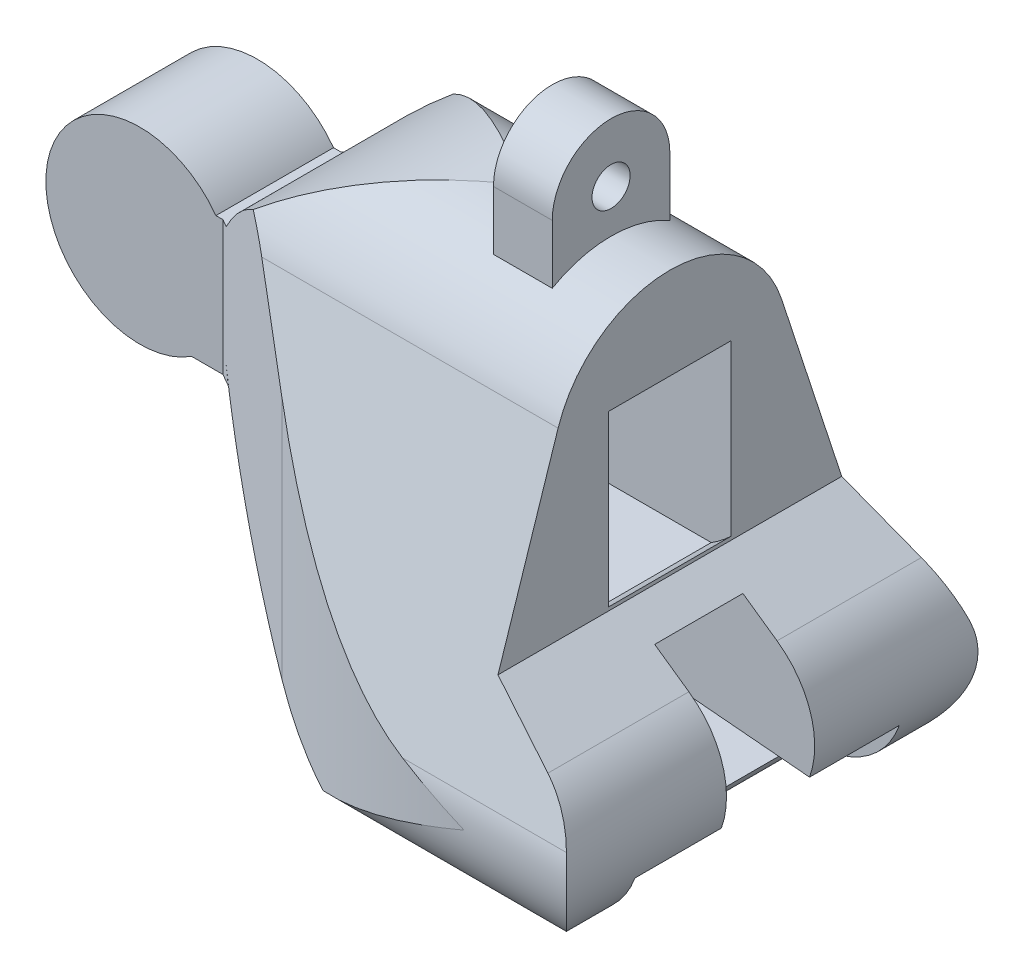
SolidWorks part; units mm, degrees
material "Polycarbonate"
ref_plane "Front Plane" through (0, 0, 0) normal (0, 0, 1) x (1, 0, 0)
ref_plane "Top Plane" through (0, 0, 0) normal (0, 1, 0) x (1, 0, 0)
ref_plane "Right Plane" through (0, 0, 0) normal (1, 0, 0) x (0, 0, -1)
sketch "Sketch2" plane through (0, 0, 0) normal (0, 0, 1) x (1, 0, 0)
  line L0 (4.4873, -2.3813) -> (4.4873, 2.3813)
  arc A0 (4.4873, 2.3813) -> (4.4873, -2.3813) centre (0, 0) ccw
  dimension "D1" = 10.16
  dimension "D2" = 4.7625
extrude "Boss-Extrude1" add sketch "Sketch2" along normal blind 6.35
sketch "Sketch3" plane through (0, 0, 0) normal (0, 0, 1) x (1, 0, 0)
  line L0 (4.4873, -2.3813) -> (4.4873, 2.3813) construction
  line L1 (4.4873, 9.525) -> (25.4423, 9.525)
  line L2 (4.4873, 9.525) -> (4.4873, -15.875)
  line L3 (4.4873, -15.875) -> (25.4423, -15.875)
  line L4 (25.4423, 9.525) -> (25.4423, -4.7625)
  line L5 (4.4873, 9.525) -> (25.4423, -15.875) construction
  line L6 (4.4873, -15.875) -> (25.4423, 9.525) construction
  line L7 (25.4423, -4.7625) -> (41.3126, -15.875)
  line L8 (41.3126, -15.875) -> (25.4423, -15.875)
  point P0 (14.9648, -3.175)
  dimension "D1" = 20.955
  dimension "D2" = 25.4
  dimension "D3" = 9.525
  dimension "D4" = 55
  dimension "D5" = 11.1125
extrude "Boss-Extrude2" add sketch "Sketch3" along normal offset from surface (22.225 mm away) 7.9375 from offset 7.9375 separate body up to face at (-0.2963, 0, 6.35) offset beyond the face yes offset against normal yes
sketch "Sketch4" plane through (0, 9.525, 0) normal (0, 1, 0) x (1, 0, 0)
  line L0 (4.4873, -6.35) -> (11.9942, -10.6841)
  line L1 (4.4873, 0) -> (11.9942, 4.3341)
  line L2 (4.4873, -14.2875) -> (4.4873, 7.9375) construction
  line L4 (25.4423, -14.2875) -> (4.4873, -14.2875) construction
  line L5 (25.4423, 7.9375) -> (4.4873, 7.9375) construction
  line L6 (4.4873, -14.2875) -> (4.4873, -6.35)
  line L7 (25.4423, 7.9375) -> (4.4873, 7.9375)
  line L8 (25.4423, -14.2875) -> (4.4873, -14.2875)
  line L9 (4.4873, 0) -> (4.4873, 7.9375)
  arc A0 (11.9942, -10.6841) -> (25.4423, -14.2875) centre (25.4423, 12.6088) ccw
  arc A1 (11.9942, 4.3341) -> (25.4423, 7.9375) centre (25.4423, -18.9588) cw
  dimension "D1" = 60
  dimension "D2" = 60
extrude "Cut-Extrude1" cut sketch "Sketch4" against normal through all
sketch "Sketch5" plane through (0, 0, 0) normal (0, 0, 1) x (1, 0, 0)
  line L0 (41.3126, -15.875) -> (25.4423, -4.7625) construction
  line L2 (11.9942, -15.875) -> (25.4423, -15.875) construction
  line L3 (22.7376, -15.875) -> (26.2079, -15.875) construction
  line L4 (25.4423, -15.875) -> (41.3126, -15.875) construction
  line L5 (41.3126, -15.875) -> (25.4423, -4.7625) construction
  line L6 (4.4873, -15.875) -> (4.4873, -2.3813)
  line L7 (25.4423, 9.525) -> (17.5048, 9.525) construction
  line L8 (25.4423, 9.525) -> (11.9942, 9.525) construction
  line L10 (4.4873, 2.3813) -> (4.4873, -2.3813) construction
  line L11 (4.4873, 2.3813) -> (4.4873, 9.525)
  line L12 (4.4873, 9.525) -> (17.5048, 9.525)
  line L13 (26.2079, -15.875) -> (41.3126, -15.875)
  line L16 (41.3126, -15.875) -> (28.9396, -7.2113)
  line L17 (4.4873, -2.3813) -> (4.8365, -3.3405)
  line L18 (4.4873, -15.875) -> (22.7376, -15.875)
  arc A1 (17.5048, 9.525) -> (4.4873, 2.3813) centre (17.5048, -5.9073) ccw
  arc A3 (4.8365, -3.3405) -> (22.7376, -15.875) centre (22.7376, 3.175) ccw
  arc A4 (26.2079, -15.875) -> (28.9396, -7.2113) centre (26.2079, -11.1125) ccw
  dimension "D1" = 20
  dimension "D2" = 7.9375
  dimension "D3" = 4.7625
  dimension "D4" = 19.05
extrude "Cut-Extrude2" cut sketch "Sketch5" along normal blind 25.24 from surface contours L18 A4 A3 L17 L6 | A4 A3 L13 L16 | A1 L12 L11 region at (8.6708, -12.2776, 0) region at (7.5722, 7.5055, 0) region at (33.8275, -13.515, 0) starting at face at (30.7324, -12.1708, -7.9375)
sketch "Sketch7" plane through (25.4423, 0, 0) normal (1, 0, 0) x (0, 0, -1)
  line L0 (-3.175, 9.525) -> (-3.175, -7.9375) construction
  line L2 (-9.525, -15.875) -> (3.175, -15.875) construction
  line L3 (3.175, -15.875) -> (7.9375, -15.875)
  line L4 (6.7396, 9.525) -> (-13.0896, 9.525) construction
  line L5 (7.9375, -4.7625) -> (7.9375, 9.525) construction
  line L10 (7.9375, 9.525) -> (-14.2875, 9.525)
  line L11 (7.9375, -4.7625) -> (7.9375, 9.525)
  line L12 (-9.525, -15.875) -> (-14.2875, -15.875)
  line L14 (-14.0509, -9.6301) -> (-9.2096, 5.1515)
  line L15 (7.7009, -9.6301) -> (2.8596, 5.1515)
  line L18 (7.9375, -4.7625) -> (7.9375, -15.875)
  line L19 (7.9375, -15.875) -> (7.9375, -4.7625)
  line L20 (-14.2875, -15.875) -> (-14.2875, 9.525)
  arc A0 (-9.2096, 5.1515) -> (2.8596, 5.1515) centre (-3.175, 3.175) cw
  arc A3 (-14.0509, -9.6301) -> (-9.525, -15.875) centre (-9.525, -11.1125) ccw
  arc A4 (7.7009, -9.6301) -> (3.175, -15.875) centre (3.175, -11.1125) cw
  point P12 (-3.175, 9.525)
  line M3 (-14.2875, 9.525) -> (-14.2875, -4.7625)
  line M5 (7.9375, -4.7625) -> (7.9375, 9.525)
  line M6 (7.9375, 9.525) -> (-14.2875, 9.525)
  line M30 (-14.2875, -4.7625) -> (7.9375, -4.7625)
  dimension "D1" = 6.35
  dimension "D2" = 4.7625
  dimension "D3" = 25.4
  dimension "D4" = 4.7625
extrude "Cut-Extrude7" cut sketch "Sketch7" against normal blind 19.05 and the other way blind 10 contours A3 L20 L12 | L19 A4 L3 region at (25.4423, -14.8112, -6.8737) region at (25.4423, -14.8112, 13.2237)
extrude "Cut-Extrude10" cut sketch "Sketch7<4>" against normal blind 17.78 and the other way blind 10.16 contours L14 A0 L10 M3 M30 | A0 L15 M6 M30 M5 | L15 A4 L18 M30 | A3 L14 L20 M30 region at (25.4423, -6.6478, -7.3305) region at (25.4423, 4.0189, -5.3307) region at (25.4423, 4.0189, 11.6807) region at (25.4423, -6.6478, 13.6805)
sketch "Sketch7<4>" plane through (25.4423, 0, 0) normal (1, 0, 0) x (0, 0, -1) same geometry as "Sketch7"
sketch "Sketch8" plane through (0, 0, 6.35) normal (0, 0, 1) x (1, 0, 0)
  line L0 (25.4423, 4.572) -> (25.4423, -4.572)
  line L2 (17.6953, 5.4005) -> (24.3758, 5.4005)
  line L3 (24.3758, -5.4005) -> (17.6953, -5.4005)
  line L4 (17.6953, 5.4005) -> (17.6953, -5.4005)
  line L5 (25.4423, -4.7625) -> (25.4423, 5.1515) construction
  arc A0 (25.4423, 4.572) -> (24.3758, 5.4005) centre (21.0356, 0) ccw
  arc A1 (25.4423, 4.572) -> (25.4423, -4.572) centre (21.0356, 0) ccw
  arc A2 (24.3758, -5.4005) -> (25.4423, -4.572) centre (21.0356, 0) ccw
  arc A3 (25.4423, 4.572) -> (25.4423, -4.572) centre (21.0356, 0) ccw
  circle A4 centre (21.0356, 0) radius 5.08 construction
  point P12 (17.6953, 0)
  dimension "D1" = 12.7
  dimension "D6" = 10.16
  dimension "D2" = 9.144
  dimension "D3" = 3.3403
extrude "Cut-Extrude8" cut sketch "Sketch8" against normal blind 6.604 from offset 0.127 contours L3 A1 L0 A0 L2 L4 region at (21.5339, 0, 6.35)
sketch "Sketch12" plane through (25.4423, 0, 0) normal (1, 0, 0) x (0, 0, -1)
  line L1 (-6.35, 8.6743) -> (0, 8.6743)
  line L2 (-6.35, 8.6743) -> (-6.35, 11.8493)
  line L4 (0, 8.6743) -> (0, 11.8493)
  arc A0 (2.8596, 5.1515) -> (-9.2096, 5.1515) centre (-3.175, 3.175) ccw construction
  arc A1 (2.8596, 5.1515) -> (-9.2096, 5.1515) centre (-3.175, 3.175) ccw construction
  arc A2 (0, 11.8493) -> (-6.35, 11.8493) centre (-3.175, 11.8493) ccw
  point P8 (-3.175, 8.6743)
  point P9 (-3.175, 9.525)
  dimension "D1" = 6.35
  dimension "D2" = 3.175
extrude "Boss-Extrude3" add sketch "Sketch12" against normal blind 3.175 from offset 3.175 offset against normal yes
hole_wizard "#1 Clearance Hole1" positions "Sketch13" profile "Sketch14" hole size "#1" standard "ANSI Inch" end condition up to next
sketch "Sketch13" plane through (22.2673, 0, 0) normal (1, 0, 0) x (0, 0, -1)
  point P0 (-3.175, 11.8493)
sketch "Sketch14" plane through (22.2673, 11.8493, 3.175) normal (0, 1, 0) x (0, 0, -1)
  line L0 (0, 0) -> (0, 3.176)
  line L1 (0, 3.176) -> (1.0287, 3.176)
  line L2 (1.0287, 3.176) -> (1.0287, 0)
  line L5 (1.0287, 0) -> (0, 0)
  line L11 (0, -6.35) -> (0, 107.95) construction
  dimension "Thru Hole Dia." = 2.0574
  dimension "Thru Hole Depth" = 3.176
ref_plane "Plane1" through (30.9704, 0, 0) normal (1, 0, 0) x (0, 0, -1)
sketch "Sketch15" plane through (30.9704, 0, 0) normal (1, 0, 0) x (0, 0, -1)
  line L1 (-5.6442, -7.2113) -> (-0.8817, -7.2113)
  line L2 (-5.6442, -7.2113) -> (-5.6442, -11.9738)
  line L3 (-5.6442, -11.9738) -> (-0.8817, -11.9738)
  line L4 (-0.8817, -7.2113) -> (-0.8817, -11.9738)
  line L5 (-5.6442, -7.2113) -> (-0.8817, -11.9738) construction
  line L6 (-5.6442, -11.9738) -> (-0.8817, -7.2113) construction
  line L7 (-13.2587, -7.2113) -> (6.9087, -7.2113) construction
  point P0 (-3.2629, -9.5925)
  dimension "D1" = 4.7625
  dimension "D2" = 4.7625
extrude "Cut-Extrude15" cut sketch "Sketch15" against normal up to surface (8.7031 mm away) up to face at (22.2673, 11.8493, 2.1463)
sketch "Sketch16" plane through (22.2673, 0, 0) normal (1, 0, 0) x (0, 0, -1)
  line L4 (-0.8817, -11.9738) -> (-0.8817, -7.2113)
  line L5 (-0.8817, -7.2113) -> (-5.6442, -7.2113)
  line L6 (-5.6442, -7.2113) -> (-5.6442, -11.9738)
  line L7 (-5.6442, -11.9738) -> (-0.8817, -11.9738)
  line L8 (-0.8817, -11.9738) -> (-0.8817, -7.2113)
  line L9 (-0.8817, -7.2113) -> (-5.6442, -7.2113)
  line L10 (-5.6442, -7.2113) -> (-5.6442, -11.9738)
  line L11 (-5.6442, -11.9738) -> (-0.8817, -11.9738)
  dimension "D1" = 0
extrude "Cut-Extrude16" cut sketch "Sketch16" against normal through all from surface starting at face at (19.0923, 11.8493, 2.1463)
hole_wizard "#1 Clearance Hole2" positions "Sketch17" profile "Sketch18" hole size "#1" standard "ANSI Inch" end condition up to next
sketch "Sketch17" plane through (22.2673, 0, 0) normal (1, 0, 0) x (0, 0, -1)
  line L8 (-0.8817, -11.9738) -> (-0.8817, -7.2113)
  line L9 (-0.8817, -7.2113) -> (-5.6442, -7.2113)
  line L10 (-5.6442, -7.2113) -> (-5.6442, -11.9738)
  line L11 (-5.6442, -11.9738) -> (-0.8817, -11.9738)
  line L12 (-0.8817, -11.9738) -> (-0.8817, -7.2113)
  line L13 (-0.8817, -7.2113) -> (-5.6442, -7.2113)
  line L14 (-5.6442, -7.2113) -> (-5.6442, -11.9738)
  line L15 (-5.6442, -11.9738) -> (-0.8817, -11.9738)
  line L16 (-5.6442, -7.2113) -> (-0.8817, -11.9738) construction
  point P0 (-3.2629, -9.5925)
  dimension "D1" = 0
sketch "Sketch18" plane through (22.2673, -9.5925, 3.2629) normal (0, 1, 0) x (0, 0, -1)
  line L0 (0, 0) -> (0, 3.176)
  line L1 (0, 3.176) -> (1.0287, 3.176)
  line L2 (1.0287, 3.176) -> (1.0287, 0)
  line L5 (1.0287, 0) -> (0, 0)
  line L11 (0, -6.35) -> (0, 107.95) construction
  dimension "Thru Hole Dia." = 2.0574
  dimension "Thru Hole Depth" = 3.176
sketch "Sketch19" plane through (0, 0, 0.8817) normal (0, 0, 1) x (1, 0, 0)
  line L0 (19.0923, -11.9738) -> (13.484, -13.4765)
  line L1 (19.0923, -7.2113) -> (6.083, -6.0731)
  line L2 (22.2673, -7.2113) -> (27.0929, -5.9183)
  line L3 (11.187, -11.9738) -> (19.0923, -11.9738)
  line L4 (19.0923, -11.9738) -> (19.0923, -7.2113)
  line L5 (19.0923, -7.2113) -> (6.768, -7.2113)
  line L6 (11.187, -11.9738) -> (19.0923, -11.9738) construction
  line L7 (19.0923, -11.9738) -> (19.0923, -7.2113)
  line L8 (19.0923, -7.2113) -> (6.768, -7.2113) construction
  line L9 (28.9396, -7.2113) -> (25.4423, -4.7625) construction
  line L10 (28.9396, -7.2113) -> (27.0929, -5.9183)
  line L11 (22.2673, -11.9738) -> (30.6941, -12.711)
  line L13 (28.9396, -7.2113) -> (22.2673, -7.2113)
  line L14 (22.2673, -7.2113) -> (22.2673, -11.9738)
  line L15 (22.2673, -11.9738) -> (30.8919, -11.9738)
  line L17 (28.9396, -7.2113) -> (22.2673, -7.2113) construction
  line L18 (22.2673, -7.2113) -> (22.2673, -11.9738)
  line L19 (22.2673, -11.9738) -> (30.8919, -11.9738) construction
  arc A1 (6.768, -7.2113) -> (11.187, -11.9738) centre (22.7376, 3.175) ccw
  arc A6 (4.8365, -3.3405) -> (11.9942, -12.5565) centre (22.7376, 3.175) ccw construction
  arc A7 (6.083, -6.0731) -> (13.484, -13.4765) centre (22.7376, 3.175) ccw
  arc A8 (26.2079, -15.875) -> (30.7338, -9.6301) centre (26.2079, -11.1125) ccw construction
  arc A9 (30.8919, -11.9738) -> (28.9396, -7.2113) centre (26.2079, -11.1125) ccw
  arc A12 (30.6941, -12.711) -> (28.9396, -7.2113) centre (26.2079, -11.1125) ccw
  dimension "D2" = 15
  dimension "D3" = 5
  dimension "D5" = 15
  dimension "D6" = 5
  dimension "D1" = 0
  dimension "D4" = 0
extrude "Cut-Extrude17" cut sketch "Sketch19" along normal up to surface (4.7625 mm away) up to face at (13.9838, -9.64, 5.6442)
sketch "Sketch21" plane through (0, 0, 0) normal (0, 0, -1) x (-1, 0, 0)
  line L0 (-4.8365, -3.3405) -> (-4.4873, -2.3813) construction
  line L1 (-5.1668, -4.2482) -> (-4.4873, -2.3813)
  line L2 (-5.1668, -4.2482) -> (-2.7856, -4.2482)
  line L3 (-4.1043, 2.9935) -> (-4.898, 2.9935)
  line L4 (-4.4873, 2.3813) -> (-4.4873, 2.9935)
  line L5 (-4.4873, -2.3813) -> (-4.4873, -4.2482)
  arc A0 (-4.4873, 2.3813) -> (-8.3449, 6.5125) centre (-17.5048, -5.9073) ccw construction
  arc A1 (-4.4873, -2.3813) -> (-4.4873, 2.3813) centre (0, 0) ccw construction
  arc A2 (-4.4873, 2.3813) -> (-4.898, 2.9935) centre (-17.5048, -5.9073) ccw
  arc A3 (-4.4873, -2.3813) -> (-2.7856, -4.2482) centre (0, 0) ccw
  arc A4 (-4.1043, 2.9935) -> (-4.4873, 2.3813) centre (0, 0) ccw
  dimension "D1" = 2.3812
  dimension "D2" = 0.7937
extrude "Boss-Extrude5" add sketch "Sketch21" along normal up to surface contours A2 L4 L3 | L5 L1 L2 region at (4.7138, -3.6259, 0) region at (4.6231, 2.7912, 0) up to face at (7.8201, -0.564, -1.9242)
extrude "Boss-Extrude6" add sketch "Sketch21<3>" against normal up to surface (6.35 mm away) contours A4 L3 A2 | L1 L2 A3 up to face at (-0.2963, 0, 6.35)
sketch "Sketch21<3>" plane through (0, 0, 0) normal (0, 0, -1) x (-1, 0, 0) same geometry as "Sketch21"
sketch "Sketch22" plane through (0, 0, 6.35) normal (0, 0, 1) x (1, 0, 0)
  line L0 (4.4873, 2.3812) -> (4.5012, 2.9935)
  line L1 (4.1043, 2.9935) -> (4.898, 2.9935) construction
  line L2 (4.5012, 2.9935) -> (4.898, 2.9935)
  line L3 (4.898, 2.9935) -> (4.4873, 2.3812)
  line L4 (4.4873, -2.3812) -> (4.4873, -4.2482)
  line L5 (5.1668, -4.2482) -> (2.7856, -4.2482) construction
  line L6 (4.4873, -4.2482) -> (5.1668, -4.2482)
  line L7 (5.1668, -4.2482) -> (4.4873, -2.3812)
extrude "Boss-Extrude8" add sketch "Sketch22" along normal up to surface (0.2371 mm away) up to face at (7.8201, -0.564, 8.2742)
sketch "Sketch28" plane through (0, 0, 0) normal (0, 0, 1) x (1, 0, 0)
  line L0 (22.2673, -11.9738) -> (30.6941, -12.711) construction
  line L1 (26.2079, -15.875) -> (22.7376, -15.875) construction
  line L2 (29.0309, -12.5655) -> (30.6941, -12.711)
  line L3 (26.2079, -15.875) -> (22.7376, -15.875)
  line L4 (13.484, -13.4765) -> (19.0923, -11.9738) construction
  line L5 (13.484, -13.4765) -> (15.8082, -12.8538)
  line L6 (26.2079, -14.2875) -> (22.7376, -14.2875)
  arc A0 (26.2079, -15.875) -> (30.7338, -9.6301) centre (26.2079, -11.1125) ccw construction
  arc A1 (11.9942, -12.5565) -> (16.1833, -14.712) centre (22.7376, 3.175) ccw construction
  arc A2 (16.1833, -14.712) -> (22.7376, -15.875) centre (22.7376, 3.175) ccw construction
  arc A4 (26.2079, -15.875) -> (30.6941, -12.711) centre (26.2079, -11.1125) ccw
  arc A5 (13.484, -13.4765) -> (16.1833, -14.712) centre (22.7376, 3.175) ccw
  arc A6 (16.1833, -14.712) -> (22.7376, -15.875) centre (22.7376, 3.175) ccw
  arc A7 (15.8082, -12.8538) -> (16.7295, -13.2214) centre (22.7376, 3.175) ccw
  arc A8 (16.7295, -13.2214) -> (22.7376, -14.2875) centre (22.7376, 3.175) ccw
  arc A9 (26.2079, -14.2875) -> (29.0309, -12.5655) centre (26.2079, -11.1125) ccw
  arc A10 (14.2551, -12.0889) -> (16.7295, -13.2214) centre (22.7376, 3.175) ccw construction
  arc A11 (26.2079, -14.2875) -> (29.1987, -12.1782) centre (26.2079, -11.1125) ccw construction
  dimension "D3" = 5
  dimension "D4" = 1.6696
  dimension "D2" = 3.4703
  dimension "D5" = 13.2227
  dimension "D1" = 1.5875
extrude "Cut-Extrude19" cut sketch "Sketch28" against normal blind 3.9688 and the other way blind 10.3187
ref_plane "Plane2" through (0, 0, -7.9375) normal (0, 0, -1) x (-1, 0, 0)
